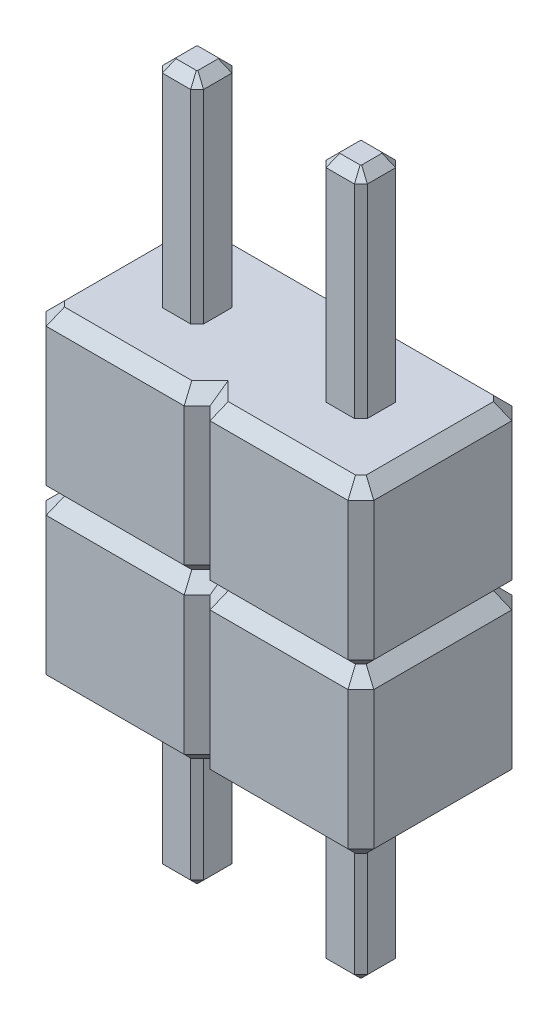
SolidWorks part; units mm, degrees
ref_plane "Спереди" through (0, 0, 0) normal (0, 0, 1) x (1, 0, 0)
ref_plane "Сверху" through (0, 0, 0) normal (0, 1, 0) x (1, 0, 0)
ref_plane "Справа" through (0, 0, 0) normal (1, 0, 0) x (0, 0, -1)
sketch "Эскиз1" plane through (0, 0, 0) normal (0, 1, 0) x (1, 0, 0)
  line L0 (0, 0) -> (0, 5470.6329) construction
  line L1 (0, 0) -> (-5470.6329, 0) construction
  line L2 (-1.59, 0.22) -> (-1.49, 0.32)
  line L3 (-1.49, -0.32) -> (-1.05, -0.32)
  line L4 (-1.59, -0.22) -> (-1.59, 0.22)
  line L5 (-1.49, 0.32) -> (-1.05, 0.32)
  line L6 (-0.95, -0.22) -> (-0.95, 0.22)
  line L7 (-1.59, -0.32) -> (-0.95, 0.32) construction
  line L8 (-1.59, 0.32) -> (-0.95, -0.32) construction
  line L9 (-2.34, 1.27) -> (-0.2, 1.27)
  line L10 (-2.54, 1.07) -> (-2.54, -1.07)
  line L11 (-2.34, -1.27) -> (-0.2, -1.27)
  line L12 (0, 1.07) -> (0, -1.07)
  line L13 (-2.54, 1.27) -> (0, -1.27) construction
  line L14 (-2.54, -1.27) -> (0, 1.27) construction
  line L15 (-1.05, 0.32) -> (-0.95, 0.22)
  line L16 (-1.05, -0.32) -> (-0.95, -0.22)
  line L17 (-1.59, -0.22) -> (-1.49, -0.32)
  line L18 (-2.54, 1.07) -> (-2.34, 1.27)
  line L19 (-0.2, 1.27) -> (0, 1.07)
  line L20 (-0.2, -1.27) -> (0, -1.07)
  line L21 (-2.54, -1.07) -> (-2.34, -1.27)
  line L22 (0.95, 0.22) -> (1.05, 0.32)
  line L23 (1.05, -0.32) -> (1.49, -0.32)
  line L24 (0.95, -0.22) -> (0.95, 0.22)
  line L25 (1.05, 0.32) -> (1.49, 0.32)
  line L26 (1.59, -0.22) -> (1.59, 0.22)
  line L27 (0.2, 1.27) -> (2.34, 1.27)
  line L28 (0, 1.07) -> (0, -1.07)
  line L29 (0.2, -1.27) -> (2.34, -1.27)
  line L30 (2.54, 1.07) -> (2.54, -1.07)
  line L31 (1.49, 0.32) -> (1.59, 0.22)
  line L32 (1.49, -0.32) -> (1.59, -0.22)
  line L33 (0.95, -0.22) -> (1.05, -0.32)
  line L34 (0, 1.07) -> (0.2, 1.27)
  line L35 (2.34, 1.27) -> (2.54, 1.07)
  line L36 (2.34, -1.27) -> (2.54, -1.07)
  line L37 (0, -1.07) -> (0.2, -1.27)
  line L38 (0.95, -0.32) -> (1.59, 0.32) construction
  line L39 (0.95, 0.32) -> (1.59, -0.32) construction
  line L40 (0, 1.27) -> (2.54, -1.27) construction
  line L41 (0, -1.27) -> (2.54, 1.27) construction
  point P5 (-1.27, 0)
  point P10 (-1.27, 0)
  point P33 (1.27, 0)
  point P38 (1.27, 0)
  dimension "D1" = 0.64
  dimension "D2" = 1.27
  dimension "D3" = 2
extrude "Бобышка-Вытянуть1" add sketch "Эскиз1" against normal blind 2.54 contours L4 L17 L3 L16 L6 L15 L5 L2 | L24 L33 L23 L32 L26 L31 L25 L22 region at (-1.27, 0, 0) region at (1.27, 0, 0)
extrude "Бобышка-Вытянуть2" add sketch "Эскиз1<3>" along normal blind 8.38 contours L4 L17 L3 L16 L6 L15 L5 L2 | L24 L33 L23 L32 L26 L31 L25 L22 region at (-1.27, 0, 0) region at (1.27, 0, 0)
sketch "Эскиз1<3>" plane through (0, 0, 0) normal (0, 1, 0) x (1, 0, 0) same geometry as "Эскиз1"
extrude "Бобышка-Вытянуть3" add sketch "Эскиз1<4>" along normal blind 2.54 contours L10 L21 L11 L20 L12 L19 L9 L18 L17 L4 L2 L5 L15 L6 L16 L3 | L12 L37 L29 L36 L30 L35 L27 L34 L33 L24 L22 L25 L31 L26 L32 L23 region at (-1.27, 0, -1.2341) region at (0.1254, 0, -1.1446)
sketch "Эскиз1<4>" plane through (0, 0, 0) normal (0, 1, 0) x (1, 0, 0) same geometry as "Эскиз1"
extrude "Бобышка-Вытянуть4" add sketch "Эскиз1<5>" along normal blind 2.54 from offset 2.54 separate body contours L10 L21 L11 L20 L12 L19 L9 L18 L17 L4 L2 L5 L15 L6 L16 L3 | L12 L37 L29 L36 L30 L35 L27 L34 L33 L24 L22 L25 L31 L26 L32 L23 region at (-1.27, 0, -1.2341) region at (0.1254, 0, -1.1446)
sketch "Эскиз1<5>" plane through (0, 0, 0) normal (0, 1, 0) x (1, 0, 0) same geometry as "Эскиз1"
chamfer "Фаска1" distance 0.15 angle 45 32 edges at (-1.54, -2.54, 0.27) (-1.27, -2.54, 0.32) (-1, -2.54, 0.27) (-0.95, -2.54, 0) (-1, -2.54, -0.27) (-1.27, -2.54, -0.32) (-1.54, -2.54, -0.27) (-1.59, -2.54, 0) (1, -2.54, 0.27) (1.27, -2.54, 0.32) (1.54, -2.54, 0.27) (1.59, -2.54, 0) (1.54, -2.54, -0.27) (1.27, -2.54, -0.32) (1, -2.54, -0.27) (0.95, -2.54, 0) (1, 8.38, -0.27) (1.27, 8.38, -0.32) (1.54, 8.38, -0.27) (1.59, 8.38, 0) (1.54, 8.38, 0.27) (1.27, 8.38, 0.32) (1, 8.38, 0.27) (0.95, 8.38, 0) (-1.54, 8.38, -0.27) (-1.27, 8.38, -0.32) (-1, 8.38, -0.27) (-0.95, 8.38, 0) (-1, 8.38, 0.27) (-1.27, 8.38, 0.32) (-1.54, 8.38, 0.27) (-1.59, 8.38, 0)
chamfer "Фаска2" distance 0.2 angle 45 28 edges at (-2.44, 2.54, -1.17) (-1.27, 2.54, -1.27) (-0.1, 2.54, -1.17) (0.1, 2.54, -1.17) (1.27, 2.54, -1.27) (2.44, 2.54, -1.17) (2.54, 2.54, 0) (2.44, 2.54, 1.17) (1.27, 2.54, 1.27) (0.1, 2.54, 1.17) (-0.1, 2.54, 1.17) (-1.27, 2.54, 1.27) (-2.44, 2.54, 1.17) (-2.54, 2.54, 0) (-2.44, 0, 1.17) (-1.27, 0, 1.27) (-0.1, 0, 1.17) (0.1, 0, 1.17) (1.27, 0, 1.27) (2.44, 0, 1.17) (2.54, 0, 0) (2.44, 0, -1.17) (1.27, 0, -1.27) (0.1, 0, -1.17) (-0.1, 0, -1.17) (-1.27, 0, -1.27) (-2.44, 0, -1.17) (-2.54, 0, 0)
chamfer "Фаска3" distance 0.2 angle 45 28 edges at (-2.44, 5.08, -1.17) (-1.27, 5.08, -1.27) (-0.1, 5.08, -1.17) (0.1, 5.08, -1.17) (1.27, 5.08, -1.27) (2.44, 5.08, -1.17) (2.54, 5.08, 0) (2.44, 5.08, 1.17) (1.27, 5.08, 1.27) (0.1, 5.08, 1.17) (-0.1, 5.08, 1.17) (-1.27, 5.08, 1.27) (-2.44, 5.08, 1.17) (-2.54, 5.08, 0) (-2.44, 2.54, 1.17) (-1.27, 2.54, 1.27) (-0.1, 2.54, 1.17) (0.1, 2.54, 1.17) (1.27, 2.54, 1.27) (2.44, 2.54, 1.17) (2.54, 2.54, 0) (2.44, 2.54, -1.17) (1.27, 2.54, -1.27) (0.1, 2.54, -1.17) (-0.1, 2.54, -1.17) (-1.27, 2.54, -1.27) (-2.44, 2.54, -1.17) (-2.54, 2.54, 0)
